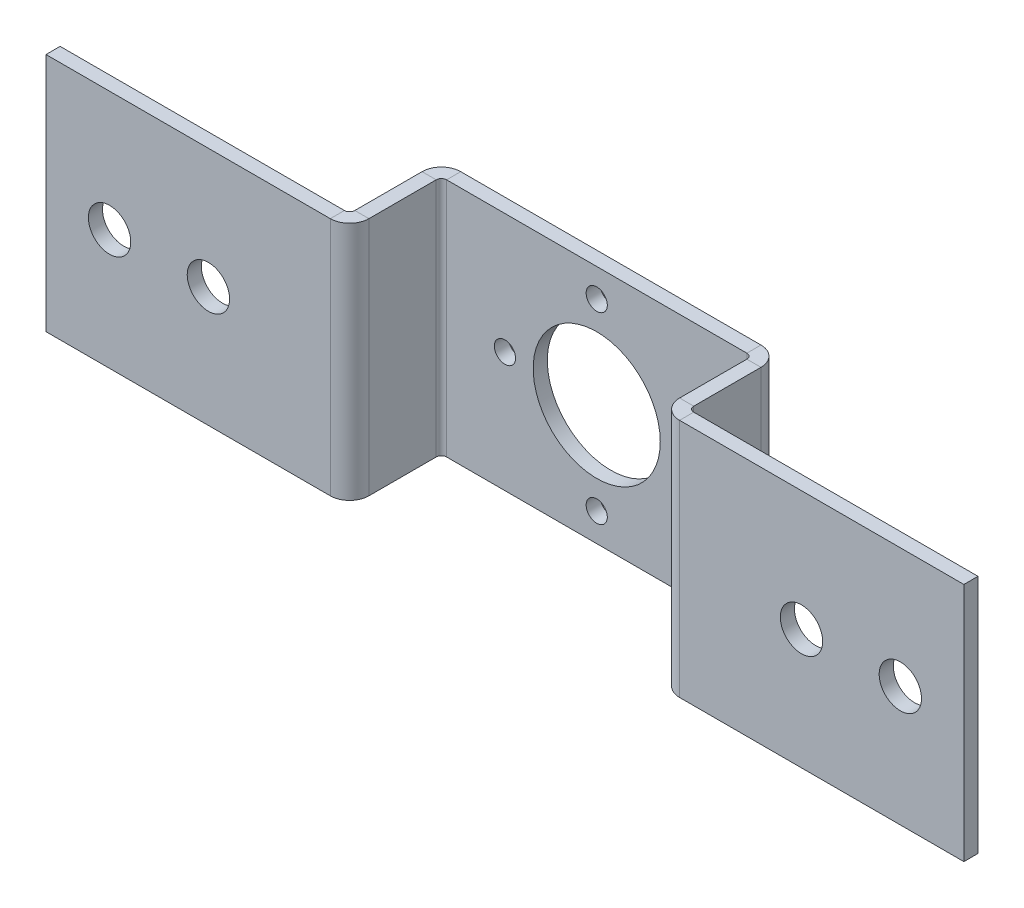
SolidWorks part; units mm, degrees
note: The reader was unsure of these and kept them because the rebuilt part matched: flange length of "Edge-Flange1", "Edge-Flange2".
material "1023 Carbon Steel Sheet (SS)"
ref_plane "Front Plane" through (0, 0, 0) normal (0, 0, 1) x (1, 0, 0)
ref_plane "Top Plane" through (0, 0, 0) normal (0, 1, 0) x (1, 0, 0)
ref_plane "Right Plane" through (0, 0, 0) normal (1, 0, 0) x (0, 0, -1)
sketch "Sketch1" plane through (0, 0, 0) normal (0, 0, 1) x (1, 0, 0)
  line L1 (-22, 17) -> (22, 17)
  line L2 (-22, 17) -> (-22, -17)
  line L3 (-22, -17) -> (22, -17)
  line L4 (22, 17) -> (22, -17)
  line L5 (-22, 17) -> (22, -17) construction
  line L6 (-22, -17) -> (22, 17) construction
  circle A0 centre (0, 0) radius 9
  circle A1 centre (0, 0) radius 13 construction
  circle A2 centre (0, 13) radius 1.5
  circle A3 centre (13, 0) radius 1.5
  circle A4 centre (0, -13) radius 1.5
  circle A5 centre (-13, 0) radius 1.5
  point P0 (0, 0)
  point P20 (0, 0)
  dimension "D3" = 18
  dimension "D4" = 26
  dimension "D5" = 3
  dimension "D1" = 44
  dimension "D2" = 34
  dimension "D6" = 4
base flange "Base-Flange1" sketch "Sketch1" thickness 2 reverse thickness direction no parameters "D1"=0.7366
edge flange "Edge-Flange1" sketch "Sketch10" flange profiles "Sketch10", "Sketch11" flange angle 90 flange length 13 flange position material outside bend radius 0.7366 thickness 2 relief rectangular parameters "D6"=10, "D8"=1
sketch "Sketch10" plane through (-22, 0, 0) normal (-1, 0, 0) x (0, -1, 0)
  line L2 (-17, 0) -> (-17, 11)
  line L3 (-17, 11) -> (17, 11)
  line L4 (17, 11) -> (17, 0)
  line L7 (-17, 0) -> (17, 0) construction
  line L8 (-17, 0) -> (17, 0)
sketch "Sketch11" plane through (22, 0, 0) normal (1, 0, 0) x (0, 1, 0)
  line L0 (-17, 0) -> (17, 0) construction
  line L1 (-17, 0) -> (17, 0)
  line L2 (-17, 0) -> (-17, 11)
  line L3 (-17, 11) -> (17, 11)
  line L4 (17, 11) -> (17, 0)
bend "EdgeBend1" bend radius 0.7366 bend angle 90 parameters "D5"=1
bend "EdgeBend2" bend radius 0.7366 bend angle 90 parameters "D5"=2
edge flange "Edge-Flange2" sketch "Sketch16" flange profiles "Sketch16", "Sketch17" flange angle 90 flange length 43 flange position material outside bend radius 0.7366 thickness 2 relief rectangular parameters "D6"=10, "D8"=1
sketch "Sketch16" plane through (-24, 0, 11) normal (0, 0, 1) x (0, 1, 0)
  line L2 (-17, 0) -> (-17, 41)
  line L3 (-17, 41) -> (17, 41)
  line L4 (17, 41) -> (17, 0)
  line L7 (-17, 0) -> (17, 0) construction
  line L8 (-17, 0) -> (17, 0)
sketch "Sketch17" plane through (24, 0, 11) normal (0, 0, 1) x (0, -1, 0)
  line L0 (-17, 0) -> (17, 0) construction
  line L1 (-17, 0) -> (17, 0)
  line L2 (-17, 0) -> (-17, 41)
  line L3 (-17, 41) -> (17, 41)
  line L4 (17, 41) -> (17, 0)
bend "EdgeBend3" bend radius 0.7366 bend angle 90 parameters "D5"=3
bend "EdgeBend4" bend radius 0.7366 bend angle 90 parameters "D5"=4
sketch "Sketch18" plane through (0, 0, 11) normal (0, 0, -1) x (-1, 0, 0)
  line L0 (0, 0) -> (65, 0) construction
  line L1 (65, 17) -> (65, -17) construction
  line L2 (0, 0) -> (0, 17) construction
  line L3 (-21.2634, 17) -> (21.2634, 17) construction
  circle A0 centre (56, 0) radius 3
  circle A1 centre (42, 0) radius 3
  circle A2 centre (-56, 0) radius 3
  circle A3 centre (-42, 0) radius 3
  dimension "D1" = 6
  dimension "D2" = 6
  dimension "D3" = 9
  dimension "D4" = 14
extrude "Cut-Extrude1" cut sketch "Sketch18" against normal blind 10 normal cut yes
sketch "Bend-Lines1" [suppressed] plane through (0, 0, 0) normal (0, 1, 0) x (1, 0, 0)
sketch "Bounding-Box1" [suppressed] plane through (0, 0, 0) normal (0, 1, 0) x (1, 0, 0)
sheet metal parameters "Sheet-Metal1" thickness 2 parameters "D1"=0.7366
flat pattern "Flat-Pattern1" [suppressed]
sketch "Bend-Lines2" plane through (0, 0, 0) normal (0, 1, 0) x (1, 0, 0)
sketch3d "Bounding-Box2" [suppressed]
  line L0 (22, -17, 0) -> (-22, -17, 0) construction
  line L1 (22, 17, 0) -> (-22, 17, 0) construction
  line L2 (22, -17, 0) -> (22, 17, 0) construction
  line L3 (-22, -17, 0) -> (-22, 17, 0) construction
sheet metal parameters "Sheet-Metal2" thickness 2 parameters "D1"=0.7366
flat pattern "Flat-Pattern1"
sketch "Bend-Lines2" plane through (0, 0, 0) normal (0, 0, 1) x (1, 0, 0)
  line L0 (22.6273, -17) -> (22.6273, 17) construction
  line L1 (-22.6273, 17) -> (-22.6273, -17) construction
  line L2 (22.6273, -17) -> (22.6273, 17) construction
  line L3 (-22.6273, 17) -> (-22.6273, -17) construction
sketch3d "Bounding-Box2" [suppressed]
  line L0 (-32.2546, -17, 0) -> (32.2546, -17, 0) construction
  line L1 (-32.2546, 17, 0) -> (32.2546, 17, 0) construction
  line L2 (-32.2546, -17, 0) -> (-32.2546, 17, 0) construction
  line L3 (32.2546, -17, 0) -> (32.2546, 17, 0) construction
bend of the flat pattern "Flatten-<EdgeBend1>1"
bend of the flat pattern "Flatten-<EdgeBend2>1"
sheet metal parameters "Sheet-Metal3" thickness 2 parameters "D1"=0.7366
flat pattern "Flat-Pattern1"
sketch "Bend-Lines2" plane through (0, 0, 0) normal (0, 0, 1) x (1, 0, 0)
  line L0 (22.6273, -17) -> (22.6273, 17) construction
  line L1 (-22.6273, 17) -> (-22.6273, -17) construction
  line L2 (22.6273, -17) -> (22.6273, 17) construction
  line L3 (-22.6273, 17) -> (-22.6273, -17) construction
  line L4 (32.882, -17) -> (32.882, 17) construction
  line L5 (-32.882, 17) -> (-32.882, -17) construction
  line L6 (32.882, -17) -> (32.882, 17) construction
  line L7 (-32.882, 17) -> (-32.882, -17) construction
sketch3d "Bounding-Box2" [suppressed]
  line L0 (-74.5093, -17, 0) -> (74.5093, -17, 0) construction
  line L1 (-74.5093, 17, 0) -> (74.5093, 17, 0) construction
  line L2 (-74.5093, -17, 0) -> (-74.5093, 17, 0) construction
  line L3 (74.5093, -17, 0) -> (74.5093, 17, 0) construction
bend of the flat pattern "Flatten-<EdgeBend1>1"
bend of the flat pattern "Flatten-<EdgeBend2>1"
bend of the flat pattern "Flatten-<EdgeBend3>1"
bend of the flat pattern "Flatten-<EdgeBend4>1"
sheet metal parameters "Sheet-Metal4" thickness 2 parameters "D1"=0.7366
flat pattern "Flat-Pattern1"
sketch "Bend-Lines2" plane through (0, 0, 0) normal (0, 0, 1) x (1, 0, 0)
  line L0 (22.6273, -17) -> (22.6273, 17) construction
  line L1 (-22.6273, 17) -> (-22.6273, -17) construction
  line L2 (22.6273, -17) -> (22.6273, 17) construction
  line L3 (-22.6273, 17) -> (-22.6273, -17) construction
  line L4 (34.882, -17) -> (34.882, 17) construction
  line L5 (-34.882, 17) -> (-34.882, -17) construction
  line L6 (34.882, -17) -> (34.882, 17) construction
  line L7 (-34.882, 17) -> (-34.882, -17) construction
sketch3d "Bounding-Box2" [suppressed]
  line L0 (-76.5093, -17, 0) -> (76.5093, -17, 0) construction
  line L1 (-76.5093, 17, 0) -> (76.5093, 17, 0) construction
  line L2 (-76.5093, -17, 0) -> (-76.5093, 17, 0) construction
  line L3 (76.5093, -17, 0) -> (76.5093, 17, 0) construction
bend of the flat pattern "Flatten-<EdgeBend1>1"
bend of the flat pattern "Flatten-<EdgeBend2>1"
bend of the flat pattern "Flatten-<EdgeBend3>1"
bend of the flat pattern "Flatten-<EdgeBend4>1"
